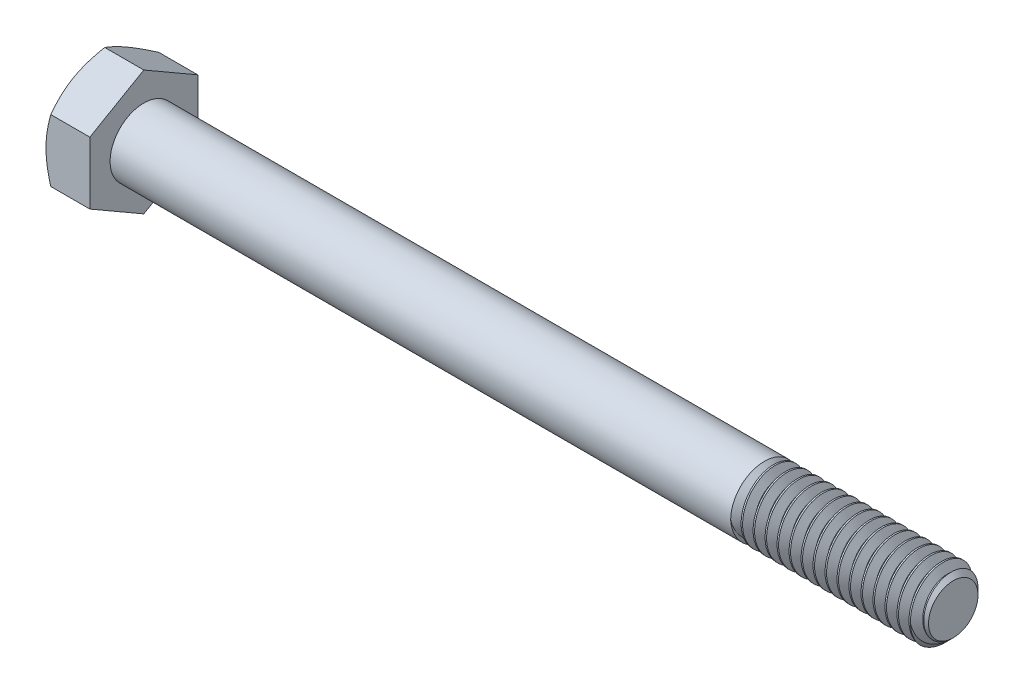
SolidWorks part; units mm, degrees
ref_plane "Front Plane" through (0, 0, 0) normal (0, 0, 1) x (1, 0, 0)
ref_plane "Top Plane" through (0, 0, 0) normal (0, 1, 0) x (1, 0, 0)
ref_plane "Right Plane" through (0, 0, 0) normal (1, 0, 0) x (0, 0, -1)
sketch "Sketch1" plane through (0, 0, 0) normal (0, 0, 1) x (1, 0, 0)
  line L0 (-50.2047, 0) -> (50.2047, 0) construction
  line L1 (50.2047, 3.9688) -> (50.2047, -3.9688) construction
  line L2 (-45.0453, 6.35) -> (-45.0453, -6.35) construction
  line L3 (-50.2047, 6.35) -> (-50.2047, -6.35) construction
  point P9 (-45.0453, 0)
  point P10 (45.2658, -3.9688)
  dimension "Screw Dia" = 7.9375
  dimension "Hex" = 12.7
  dimension "Head Ht" = 5.1594
  dimension "Screw Lenght" = 95.25
  dimension "D1" = 4.9389
ref_plane "Plane2" through (50.2047, 0, 0) normal (1, 0, 0) x (0, 0, -1)
sketch "Sketch5" plane through (50.2047, 0, 0) normal (1, 0, 0) x (0, 0, -1)
  circle A0 centre (0, 0) radius 3.9688
extrude "Boss-Extrude3" add sketch "Sketch5" against normal up to vertex (95.25 mm away) up to point (-45.0453, 0, 0)
sketch "Sketch9" plane through (50.2047, 0, 0) normal (1, 0, 0) x (0, 0, -1)
  circle A1 centre (0, 0) radius 3.9688
  circle A2 centre (0, 0) radius 3.9688
  dimension "D1" = 0
curve "Helix/Spiral1" pitch 1.4111 height 23.6361 turns 16.75 parameters "Pitch"=1.4111
chamfer "Chamfer1" distance 1.0583 angle 45 1 edges at (50.2047, 0, -3.9688)
sketch "Sketch10" plane through (0, 0, 0) normal (0, 0, 1) x (1, 0, 0)
  line L0 (50.2047, 3.9688) -> (50.7339, 3.0522)
  line L1 (50.7339, 3.0522) -> (50.9102, 3.0522)
  line L2 (50.9102, 3.0522) -> (51.4394, 3.9687)
  line L3 (50.2047, 3.9688) -> (51.4394, 3.9687)
  line L4 (50.822, 3.9688) -> (50.822, 3.0522) construction
  line L5 (50.4693, 3.5105) -> (51.1748, 3.5105) construction
  dimension "D1" = 60
  dimension "D2" = 0.1764
  dimension "D3" = 0.7056
sweep "Cut-Sweep1" cut profiles "Sketch10" path "Helix/Spiral1" align with end faces yes
sketch "Sketch11" plane through (0, 0, 0) normal (0, 0, 1) x (1, 0, 0)
  line L0 (-45.0453, 3.9688) -> (-45.0453, 0)
  line L1 (-45.0453, 0) -> (31.9484, 0)
  line L3 (31.9484, 0) -> (27.9797, 3.9688)
  line L4 (-45.0453, 3.9688) -> (27.9797, 3.9688)
  dimension "D1" = 45
  dimension "MIn Thread" = 22.225
revolve "Revolve1" add sketch "Sketch11" angle 360 about L1
sketch "Sketch6" plane through (-45.0453, 0, 0) normal (-1, 0, 0) x (0, 0, 1)
  line L0 (0, 6.35) -> (0, -6.35) construction
  line L1 (6.35, 3.6662) -> (0, 7.3323)
  line L2 (0, 7.3323) -> (-6.35, 3.6662)
  line L3 (-6.35, 3.6662) -> (-6.35, -3.6662)
  line L4 (-6.35, -3.6662) -> (0, -7.3323)
  line L5 (0, -7.3323) -> (6.35, -3.6662)
  line L6 (6.35, -3.6662) -> (6.35, 3.6662)
  circle A0 centre (0, 0) radius 6.35 construction
extrude "Boss-Extrude4" add sketch "Sketch6" along normal up to vertex (5.1594 mm away) up to point (-50.2047, -6.35, 0)
sketch "Sketch7" plane through (-50.2047, 0, 0) normal (-1, 0, 0) x (0, 0, 1)
  circle A0 centre (0, 0) radius 6.35 construction
  circle A1 centre (0, 0) radius 6.35
sketch "Sketch8" plane through (-50.2047, 0, 0) normal (-1, 0, 0) x (0, 0, 1)
  circle A0 centre (0, 0) radius 6.35 construction
  circle A1 centre (0, 0) radius 6.35
extrude "Cut-Extrude3" cut sketch "Sketch8" against normal through all draft 60 flip side to cut
sketch "Sketch12" plane through (-50.2047, 0, 0) normal (-1, 0, 0) x (0, 0, 1)
  line L0 (0, 4.8895) -> (0, 2.7305) construction
  line L1 (0.1905, 4.8895) -> (0.1905, 2.7305)
  line L2 (-0.1905, 4.8895) -> (-0.1905, 2.7305)
  line L3 (0, 3.9688) -> (0, -3.9688) construction
  arc A0 (0.1905, 4.8895) -> (-0.1905, 4.8895) centre (0, 4.8895) ccw
  arc A1 (-0.1905, 2.7305) -> (0.1905, 2.7305) centre (0, 2.7305) ccw
  circle A3 centre (0, 0) radius 2.54 construction
  circle A4 centre (0, 0) radius 5.08 construction
  point P2 (0, 3.81)
  dimension "D1" = 5.08
  dimension "D3" = 10.16
  dimension "D2" = 0.381
extrude "Cut-Extrude4" cut sketch "Sketch12" against normal blind 0.254
pattern_circular "CirPattern1" count 3 over 360 about axis through (0, 0, 0) along (1, 0, 0) of "Cut-Extrude4"
equation "\"D2@Sketch10\" = \"Pitch@Helix/Spiral1\"*.125"
equation "\"D3@Sketch10\" = \"Pitch@Helix/Spiral1\"*.5"
equation "\"D3@Helix/Spiral1\" = \"MIn Thread@Sketch11\"+\"Pitch@Helix/Spiral1\""
equation "\"D1@Chamfer1\" = \"Pitch@Helix/Spiral1\"*.75"
equation "\"D1@Sketch12\" = \"Hex@Sketch1\"*.4"
equation "\"D3@Sketch12\" = \"Hex@Sketch1\"*.8"
equation "\"D2@Sketch12\" = \"Hex@Sketch1\"*.03"
equation "\"D1@Sketch1\" = \"Pitch@Helix/Spiral1\"*3.5"
